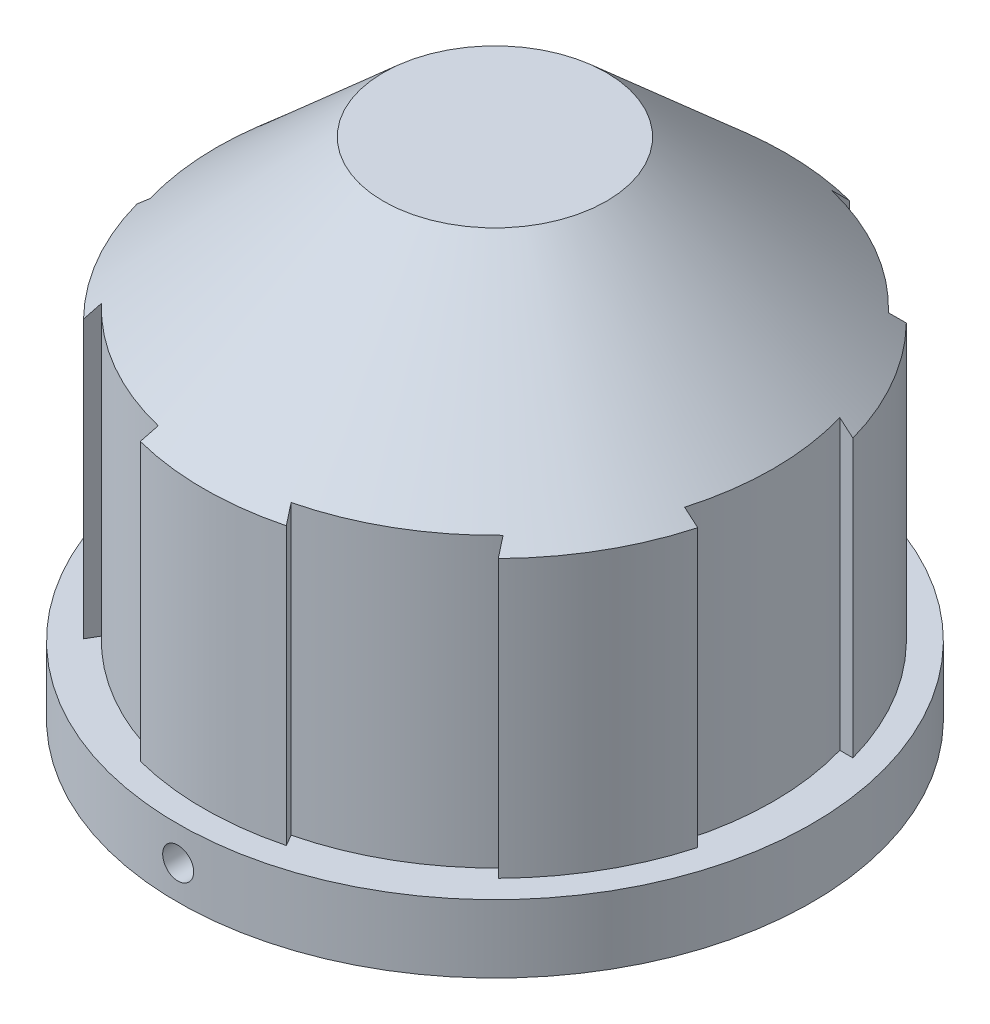
SolidWorks part; units mm, degrees
ref_plane "Front Plane" through (0, 0, 0) normal (0, 0, 1) x (1, 0, 0)
ref_plane "Top Plane" through (0, 0, 0) normal (0, 1, 0) x (1, 0, 0)
ref_plane "Right Plane" through (0, 0, 0) normal (1, 0, 0) x (0, 0, -1)
sketch "Sketch1" plane through (0, 0, 0) normal (0, 0, 1) x (1, 0, 0)
  line L0 (16.35, 0) -> (16.35, 3.5)
  line L1 (16.35, 3.5) -> (15, 3.5)
  line L2 (15, 3.5) -> (15, 17.7785)
  line L3 (15, 17.7785) -> (5.75, 26)
  line L4 (5.75, 26) -> (-0.0162, 26)
  line L5 (0, 0) -> (0, 31.4223) construction
  line L6 (16.35, 0) -> (12.75, 0)
  line L7 (12.75, 0) -> (12.75, 17.1025)
  line L8 (12.75, 17.1025) -> (5.6965, 23.3717)
  line L9 (5.6965, 23.3717) -> (4.5, 5)
  line L10 (4.5, 5) -> (3.425, 5)
  line L11 (3.425, 5) -> (3.0846, 24.5)
  line L12 (3.0846, 24.5) -> (0, 24.5)
  line L13 (0, 24.5) -> (-0.0162, 26)
  dimension "D1" = 32.7
  dimension "D2" = 3.5
  dimension "D3" = 25.5
  dimension "D4" = 6.85
  dimension "D5" = 9
  dimension "D6" = 11.5
  dimension "D7" = 30
  dimension "D8" = 91
  dimension "D9" = 2
  dimension "D10" = 24.5
  dimension "D11" = 26
  dimension "D12" = 5
revolve "Revolve3" add sketch "Sketch1" angle 360 about L5 region at (14.55, 0.3071, 0)
sketch "Sketch2" plane through (0, 26, 0) normal (0, 1, 0) x (1, 0, 0)
  line L0 (14.35, 0) -> (15, 0) construction
  line L1 (13.7812, -4) -> (14.4568, -4)
  line L2 (13.7812, 4) -> (14.4568, 4)
  line L3 (0, 4) -> (20.7165, 4) construction
  line L4 (0, 0) -> (20.7165, 0) construction
  line L5 (0, -4) -> (20.7165, -4) construction
  arc A0 (14.4568, -4) -> (14.4568, 4) centre (0, 0) ccw
  arc A1 (13.7812, -4) -> (13.7812, 4) centre (0, 0) ccw
  dimension "D1" = 28.7
  dimension "D2" = 4
  dimension "D3" = 4
extrude "Cut-Extrude1" cut sketch "Sketch2" against normal up to surface (22.5 mm away) up to face at (0, 3.5, -15)
pattern_circular "CirPattern1" count 6 over 360 about axis through (0, 26, 0) along (0, -1, 0) of "Cut-Extrude1"
ref_plane "Plane1" through (0, 0, 16.35) normal (0, 0, 1) x (1, 0, 0)
hole_wizard "M2x0.4 Tapped Hole1" positions "Sketch3" profile "Sketch4" tap size "M2x0.4" standard "ANSI Metric"
sketch "Sketch3" plane through (0, 0, 16.35) normal (0, 0, 1) x (1, 0, 0)
  point P0 (0, 1.75)
  dimension "D1" = 1.75
sketch "Sketch4" plane through (0, 1.75, 16.35) normal (1, 0, 0) x (0, -1, 0)
  line L0 (0, 0) -> (0, 7.4807)
  line L1 (0, 7.4807) -> (0.8, 7)
  line L2 (0.8, 7) -> (0.8, 0)
  line L5 (0.8, 0) -> (0, 0)
  line L10 (0, 7.4807) -> (-0.8, 7) construction
  line L11 (0, -6.35) -> (0, 107.95) construction
  dimension "Tap Drill Dia." = 1.6
  dimension "Tap Drill Depth" = 7
  dimension "Drill Angle" = 118
cosmetic thread "Hole Thread1" parameters "D1"=3.6251, "D2"=2
ref_plane "Plane2" through (0, 0, -16.35) normal (0, 0, -1) x (-1, 0, 0)
hole_wizard "M2x0.4 Tapped Hole2" positions "Sketch5" profile "Sketch6" tap size "M2x0.4" standard "ANSI Metric"
sketch "Sketch5" plane through (0, 0, -16.35) normal (0, 0, -1) x (-1, 0, 0)
  point P0 (0, 1.75)
  dimension "D1" = 1.75
sketch "Sketch6" plane through (0, 1.75, -16.35) normal (1, 0, 0) x (0, 1, 0)
  line L0 (0, 0) -> (0, 8.6807)
  line L1 (0, 8.6807) -> (0.8, 8.2)
  line L2 (0.8, 8.2) -> (0.8, 0)
  line L5 (0.8, 0) -> (0, 0)
  line L10 (0, 8.6807) -> (-0.8, 8.2) construction
  line L11 (0, -6.35) -> (0, 107.95) construction
  dimension "Tap Drill Dia." = 1.6
  dimension "Tap Drill Depth" = 8.2
  dimension "Drill Angle" = 118
cosmetic thread "Hole Thread2" parameters "D1"=3.6251, "D2"=2
thread "Thread1" pitch 2 method cut profile "Thread Profile1" start angle 0, offset 3, length 18, pitch 2, diameter 25.5
ref_plane "Plane3" through (12.75, -3, 0) normal (0, 0, 1) x (1, 0, 0)
sketch "Thread Profile1" plane through (12.75, -3, 0) normal (0, 0, 1) x (1, 0, 0)
  line L0 (0, 0) -> (0, 2) construction
  line L1 (0, 0) -> (1.0825, 0.625)
  line L2 (1.0825, 0.625) -> (1.0825, 0.875)
  line L3 (1.0825, 0.875) -> (0, 1.5)
  line L4 (1.0825, 0.75) -> (0, 0.75) construction
  line L11 (0, 0) -> (0, 1.5)
  point P2 (0, 0)
  dimension "Pitch" = 2
  dimension "Profile_Angle" = 60
  dimension "Profile_Land" = 0.25
  dimension "Profile_Height" = 1.0825
